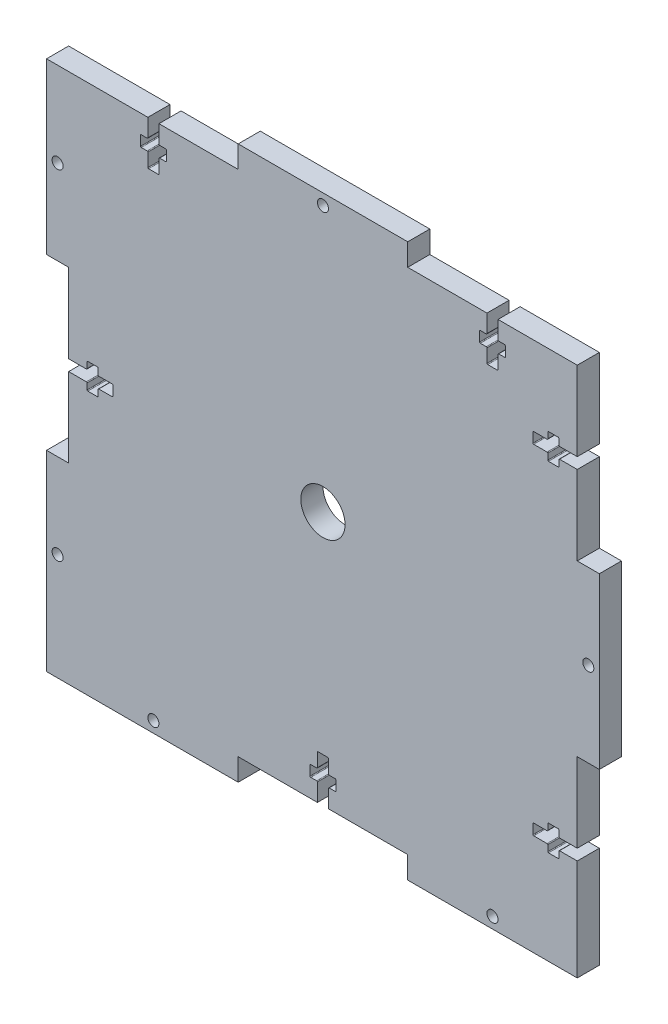
SolidWorks part; units mm, degrees
ref_plane "Front Plane" through (0, 0, 0) normal (0, 0, 1) x (1, 0, 0)
ref_plane "Top Plane" through (0, 0, 0) normal (0, 1, 0) x (1, 0, 0)
ref_plane "Right Plane" through (0, 0, 0) normal (1, 0, 0) x (0, 0, -1)
sketch "Sketch1" plane through (0, 0, 0) normal (0, 0, 1) x (1, 0, 0)
  line L0 (-69, 69) -> (-23, 69)
  line L5 (-75, -75) -> (75, -75) construction
  line L6 (-75, -75) -> (-75, 75) construction
  line L7 (-75, 75) -> (75, 75) construction
  line L8 (75, -75) -> (75, 75) construction
  line L9 (75, 23) -> (69, 23)
  line L10 (69, -23) -> (75, -23)
  line L11 (-69, -69) -> (69, -69) construction
  line L12 (-69, -69) -> (-69, 69) construction
  line L13 (-69, 69) -> (69, 69) construction
  line L14 (69, -69) -> (69, 69) construction
  line L15 (-69, -69) -> (69, 69) construction
  line L16 (69, -69) -> (69, -23)
  line L17 (-23, 69) -> (-23, 75)
  line L18 (-23, 75) -> (23, 75)
  line L19 (23, 75) -> (23, 69)
  line L20 (23, 69) -> (69, 69)
  line L21 (75, -23) -> (75, 23)
  line L22 (69, 23) -> (69, 69)
  line L23 (-75, 23) -> (-69, 23)
  line L24 (-69, 69) -> (-75, 69)
  line L25 (-75, 69) -> (-75, 23)
  line L26 (69, -69) -> (69, -75)
  line L27 (69, -75) -> (23, -75)
  line L28 (23, -75) -> (23, -69)
  line L29 (23, -69) -> (-23, -69)
  line L30 (-23, -69) -> (-23, -75)
  line L31 (-23, -75) -> (-69, -75)
  line L32 (-69, -75) -> (-69, -69) construction
  line L33 (-69, 23) -> (-69, -23)
  line L34 (-69, -23) -> (-75, -23)
  line L35 (-75, -23) -> (-75, -69)
  line L36 (-75, -69) -> (-69, -69) construction
  line L37 (-46, 69) -> (-46, -75) construction
  line L38 (-69, 69) -> (69, -69) construction
  line L39 (-75, -75) -> (-69, -75)
  line L40 (-75, -75) -> (-75, -69)
  point P0 (0, 0)
  point P6 (-7, -7)
  point P26 (0, -75)
  point P27 (-75, 0)
  dimension "D1" = 150
  dimension "D2" = 150
  dimension "D5" = 46
  dimension "D3" = 6
  dimension "D6" = 6
  dimension "D7" = 6
extrude "Box Side" add sketch "Sketch1" along normal blind 6
sketch "Sketch2" plane through (0, 0, 6) normal (0, 0, 1) x (1, 0, 0)
  line L0 (23, 72) -> (-23, 72) construction
  line L1 (23, 75) -> (23, 69) construction
  line L2 (-23, 69) -> (-23, 75) construction
  line L3 (-46, 69) -> (-46, -75) construction
  line L5 (0, 75) -> (0, 69) construction
  line L6 (-23, 75) -> (23, 75) construction
  line L7 (-69, 69) -> (69, 69) construction
  line L16 (-46, 69) -> (-46, -75) construction
  line L21 (0, -69) -> (0, 69) construction
  line L35 (-69, 69) -> (-23, 69) construction
  line L36 (-44.5, 69) -> (-44.5, 64.2)
  line L37 (-44.3, 64) -> (-42.7, 64)
  line L38 (-42.5, 63.8) -> (-42.5, 61.2)
  line L39 (-42.7, 61) -> (-44.3, 61)
  line L40 (-44.5, 60.8) -> (-44.5, 57.2)
  line L46 (-44.7, 57) -> (-47.3, 57)
  line L48 (-44.5, 69) -> (-47.5, 69)
  line L51 (-47.5, 60.8) -> (-47.5, 57.2)
  line L52 (-49.3, 61) -> (-47.7, 61)
  line L53 (-49.5, 63.8) -> (-49.5, 61.2)
  line L54 (-47.7, 64) -> (-49.3, 64)
  line L55 (-47.5, 69) -> (-47.5, 64.2)
  line L56 (47.5, 69) -> (47.5, 64.2)
  line L57 (47.7, 64) -> (49.3, 64)
  line L58 (49.5, 63.8) -> (49.5, 61.2)
  line L59 (49.3, 61) -> (47.7, 61)
  line L60 (47.5, 60.8) -> (47.5, 57.2)
  line L61 (44.5, 69) -> (47.5, 69)
  line L62 (44.7, 57) -> (47.3, 57)
  line L63 (44.5, 60.8) -> (44.5, 57.2)
  line L64 (42.7, 61) -> (44.3, 61)
  line L65 (42.5, 63.8) -> (42.5, 61.2)
  line L66 (44.3, 64) -> (42.7, 64)
  line L67 (44.5, 69) -> (44.5, 64.2)
  line L68 (-69, -69) -> (69, 69) construction
  line L69 (-69, -69) -> (69, 69) construction
  line L70 (75, 0) -> (69, 0) construction
  line L71 (72, 23) -> (72, -23) construction
  line L72 (69, 44.5) -> (64.2, 44.5)
  line L73 (64, 44.3) -> (64, 42.7)
  line L74 (63.8, 42.5) -> (61.2, 42.5)
  line L75 (61, 42.7) -> (61, 44.3)
  line L76 (60.8, 44.5) -> (57.2, 44.5)
  line L77 (57, 44.7) -> (57, 47.3)
  line L78 (69, 44.5) -> (69, 47.5)
  line L79 (60.8, 47.5) -> (57.2, 47.5)
  line L80 (61, 49.3) -> (61, 47.7)
  line L81 (63.8, 49.5) -> (61.2, 49.5)
  line L82 (64, 47.7) -> (64, 49.3)
  line L83 (69, 47.5) -> (64.2, 47.5)
  line L84 (69, -47.5) -> (64.2, -47.5)
  line L85 (64, -47.7) -> (64, -49.3)
  line L86 (63.8, -49.5) -> (61.2, -49.5)
  line L87 (61, -49.3) -> (61, -47.7)
  line L88 (60.8, -47.5) -> (57.2, -47.5)
  line L89 (69, -44.5) -> (69, -47.5)
  line L90 (57, -44.7) -> (57, -47.3)
  line L91 (60.8, -44.5) -> (57.2, -44.5)
  line L92 (61, -42.7) -> (61, -44.3)
  line L93 (63.8, -42.5) -> (61.2, -42.5)
  line L94 (64, -44.3) -> (64, -42.7)
  line L95 (69, -44.5) -> (64.2, -44.5)
  line L120 (-69, 69) -> (69, -69) construction
  line L121 (-69, 69) -> (69, -69) construction
  line L122 (-1.5, -69) -> (1.5, -69)
  line L123 (-23, -69) -> (23, -69) construction
  line L124 (1.5, -69) -> (1.5, -64.2)
  line L125 (1.7, -64) -> (3.3, -64)
  line L126 (3.5, -63.8) -> (3.5, -61.2)
  line L127 (3.3, -61) -> (1.7, -61)
  line L128 (1.5, -60.8) -> (1.5, -57.2)
  line L129 (1.3, -57) -> (-1.3, -57)
  line L130 (-1.5, -60.8) -> (-1.5, -57.2)
  line L131 (-3.3, -61) -> (-1.7, -61)
  line L132 (-3.5, -63.8) -> (-3.5, -61.2)
  line L133 (-1.7, -64) -> (-3.3, -64)
  line L134 (-1.5, -69) -> (-1.5, -64.2)
  line L135 (-69, -1.5) -> (-64.2, -1.5)
  line L136 (-64, -1.7) -> (-64, -3.3)
  line L137 (-63.8, -3.5) -> (-61.2, -3.5)
  line L138 (-61, -3.3) -> (-61, -1.7)
  line L139 (-60.8, -1.5) -> (-57.2, -1.5)
  line L140 (-57, 1.3) -> (-57, -1.3)
  line L141 (-60.8, 1.5) -> (-57.2, 1.5)
  line L142 (-61, 3.3) -> (-61, 1.7)
  line L143 (-63.8, 3.5) -> (-61.2, 3.5)
  line L144 (-64, 1.7) -> (-64, 3.3)
  line L145 (-69, 1.5) -> (-64.2, 1.5)
  line L146 (-69, -1.5) -> (-69, 1.5)
  line L147 (-69, -72) -> (-23, -72) construction
  line L148 (-23, 69) -> (-75, 69) construction
  line L149 (-23, -75) -> (-23, -69) construction
  line L150 (-69, -69) -> (-69, -75) construction
  line L151 (-75, -75) -> (-23, -75) construction
  circle A0 centre (0, 72) radius 1.5
  arc A1 (-44.5, 57.2) -> (-44.7, 57) centre (-44.7, 57.2) cw
  arc A2 (-44.3, 61) -> (-44.5, 60.8) centre (-44.3, 60.8) ccw
  arc A3 (-42.5, 61.2) -> (-42.7, 61) centre (-42.7, 61.2) cw
  arc A4 (-42.7, 64) -> (-42.5, 63.8) centre (-42.7, 63.8) cw
  arc A5 (-44.5, 64.2) -> (-44.3, 64) centre (-44.3, 64.2) ccw
  arc A6 (-47.5, 64.2) -> (-47.7, 64) centre (-47.7, 64.2) cw
  arc A7 (-49.3, 64) -> (-49.5, 63.8) centre (-49.3, 63.8) ccw
  arc A8 (-49.5, 61.2) -> (-49.3, 61) centre (-49.3, 61.2) ccw
  arc A9 (-47.7, 61) -> (-47.5, 60.8) centre (-47.7, 60.8) cw
  arc A10 (-47.5, 57.2) -> (-47.3, 57) centre (-47.3, 57.2) ccw
  arc A11 (47.5, 57.2) -> (47.3, 57) centre (47.3, 57.2) cw
  arc A12 (47.7, 61) -> (47.5, 60.8) centre (47.7, 60.8) ccw
  arc A13 (49.5, 61.2) -> (49.3, 61) centre (49.3, 61.2) cw
  arc A14 (49.3, 64) -> (49.5, 63.8) centre (49.3, 63.8) cw
  arc A15 (47.5, 64.2) -> (47.7, 64) centre (47.7, 64.2) ccw
  arc A16 (44.5, 64.2) -> (44.3, 64) centre (44.3, 64.2) cw
  arc A17 (42.7, 64) -> (42.5, 63.8) centre (42.7, 63.8) ccw
  arc A18 (42.5, 61.2) -> (42.7, 61) centre (42.7, 61.2) ccw
  arc A19 (44.3, 61) -> (44.5, 60.8) centre (44.3, 60.8) cw
  arc A20 (44.5, 57.2) -> (44.7, 57) centre (44.7, 57.2) ccw
  arc A21 (57.2, 44.5) -> (57, 44.7) centre (57.2, 44.7) cw
  arc A22 (61, 44.3) -> (60.8, 44.5) centre (60.8, 44.3) ccw
  arc A23 (61.2, 42.5) -> (61, 42.7) centre (61.2, 42.7) cw
  arc A24 (64, 42.7) -> (63.8, 42.5) centre (63.8, 42.7) cw
  arc A25 (64.2, 44.5) -> (64, 44.3) centre (64.2, 44.3) ccw
  arc A26 (64.2, 47.5) -> (64, 47.7) centre (64.2, 47.7) cw
  arc A27 (64, 49.3) -> (63.8, 49.5) centre (63.8, 49.3) ccw
  arc A28 (61.2, 49.5) -> (61, 49.3) centre (61.2, 49.3) ccw
  arc A29 (61, 47.7) -> (60.8, 47.5) centre (60.8, 47.7) cw
  arc A30 (57.2, 47.5) -> (57, 47.3) centre (57.2, 47.3) ccw
  arc A31 (57.2, -47.5) -> (57, -47.3) centre (57.2, -47.3) cw
  arc A32 (61, -47.7) -> (60.8, -47.5) centre (60.8, -47.7) ccw
  arc A33 (61.2, -49.5) -> (61, -49.3) centre (61.2, -49.3) cw
  arc A34 (64, -49.3) -> (63.8, -49.5) centre (63.8, -49.3) cw
  arc A35 (64.2, -47.5) -> (64, -47.7) centre (64.2, -47.7) ccw
  arc A36 (64.2, -44.5) -> (64, -44.3) centre (64.2, -44.3) cw
  arc A37 (64, -42.7) -> (63.8, -42.5) centre (63.8, -42.7) ccw
  arc A38 (61.2, -42.5) -> (61, -42.7) centre (61.2, -42.7) ccw
  arc A39 (61, -44.3) -> (60.8, -44.5) centre (60.8, -44.3) cw
  arc A40 (57.2, -44.5) -> (57, -44.7) centre (57.2, -44.7) ccw
  circle A41 centre (72, 0) radius 1.5
  arc A62 (1.5, -57.2) -> (1.3, -57) centre (1.3, -57.2) ccw
  arc A63 (1.7, -61) -> (1.5, -60.8) centre (1.7, -60.8) cw
  arc A64 (3.5, -61.2) -> (3.3, -61) centre (3.3, -61.2) ccw
  arc A65 (3.3, -64) -> (3.5, -63.8) centre (3.3, -63.8) ccw
  arc A66 (1.5, -64.2) -> (1.7, -64) centre (1.7, -64.2) cw
  arc A67 (-1.5, -64.2) -> (-1.7, -64) centre (-1.7, -64.2) ccw
  arc A68 (-3.3, -64) -> (-3.5, -63.8) centre (-3.3, -63.8) cw
  arc A69 (-3.5, -61.2) -> (-3.3, -61) centre (-3.3, -61.2) cw
  arc A70 (-1.7, -61) -> (-1.5, -60.8) centre (-1.7, -60.8) ccw
  arc A71 (-1.5, -57.2) -> (-1.3, -57) centre (-1.3, -57.2) cw
  arc A72 (-57.2, -1.5) -> (-57, -1.3) centre (-57.2, -1.3) ccw
  arc A73 (-61, -1.7) -> (-60.8, -1.5) centre (-60.8, -1.7) cw
  arc A74 (-61.2, -3.5) -> (-61, -3.3) centre (-61.2, -3.3) ccw
  arc A75 (-64, -3.3) -> (-63.8, -3.5) centre (-63.8, -3.3) ccw
  arc A76 (-64.2, -1.5) -> (-64, -1.7) centre (-64.2, -1.7) cw
  arc A77 (-64.2, 1.5) -> (-64, 1.7) centre (-64.2, 1.7) ccw
  arc A78 (-64, 3.3) -> (-63.8, 3.5) centre (-63.8, 3.3) cw
  arc A79 (-61.2, 3.5) -> (-61, 3.3) centre (-61.2, 3.3) cw
  arc A80 (-61, 1.7) -> (-60.8, 1.5) centre (-60.8, 1.7) ccw
  arc A81 (-57.2, 1.5) -> (-57, 1.3) centre (-57.2, 1.3) cw
  circle A82 centre (-46, -72) radius 1.5
  circle A83 centre (46, -72) radius 1.5
  circle A84 centre (-72, 46) radius 1.5
  circle A85 centre (-72, -46) radius 1.5
  point P6 (0, 72)
  point P38 (0, 0)
  point P56 (-46, 57)
  point P88 (46, 57)
  point P161 (57, 46)
  point P162 (57, -46)
  point P198 (0, -57)
  point P231 (-57, 0)
  point P234 (-42.5, 62.5)
  dimension "D1" = 3
  dimension "D2" = 0.2
  dimension "D8" = 0.2
  dimension "D14" = 3
  dimension "D4" = 3
  dimension "D7" = 1.5
  dimension "D10" = 3
  dimension "D12" = 1.5
  dimension "D9" = 12
  dimension "D11" = 5
  dimension "D13" = 7
  dimension "D3" = 12
  dimension "D5" = 7
  dimension "D6" = 5
extrude "Screw Cut-outs" cut sketch "Sketch2" against normal through all
sketch "Sketch3" plane through (0, 0, 6) normal (0, 0, 1) x (1, 0, 0)
  line L0 (-69, -69) -> (69, 69) construction
  line L1 (-69, -69) -> (69, 69) construction
  line L2 (-69, 69) -> (69, -69) construction
  line L3 (-69, 69) -> (69, -69) construction
  circle A0 centre (0, 0) radius 6
  point P4 (0, 0)
  dimension "D1" = 12
extrude "BearingHole" cut sketch "Sketch3" against normal through all
equation "\"filletRadius\"=0.2"
equation "\"D8@Sketch2\"=\"filletRadius\""
equation "\"D2@Sketch2\"=\"filletRadius\""
equation "\"fingerWidth\"= 46"
equation "\"D5@Sketch1\"=\"fingerWidth\""
equation "\"wallThickness\"= 6"
equation "\"D3@Sketch1\" = \"wallThickness\""
equation "\"D6@Sketch1\" = \"wallThickness\""
equation "\"D7@Sketch1\" = \"wallThickness\""
equation "\"D1@Box Side\" = \"wallThickness\""
equation "\"M3\"= 3"
equation "\"D14@Sketch2\"=\"M3\""
equation "\"D1@Sketch2\"=\"M3\""
equation "\"D12@Sketch2\"=\"M3\"/2"
equation "\"nutThickness\"=3"
equation "\"D10@Sketch2\" = \"nutThickness\""
equation "\"boltLength\"= 12"
equation "\"D9@Sketch2\" = \"boltLength\""
equation "\"distanceToNut\"= 5"
equation "\"D11@Sketch2\" = \"distanceToNut\""
equation "\"D13@Sketch2\" = \"nutWidth\""
equation "\"D7@Sketch2\"=\"M3\"/2"
equation "\"D4@Sketch2\" = \"nutThickness\""
equation "\"D3@Sketch2\" = \"boltLength\""
equation "\"D5@Sketch2\" = \"nutWidth\""
equation "\"D6@Sketch2\" = \"distanceToNut\""
equation "\"sideLength\"=150"
equation "\"D1@Sketch1\"=\"sideLength\""
equation "\"D2@Sketch1\"=\"sideLength\""
equation "\"nutWidth\"=7"
